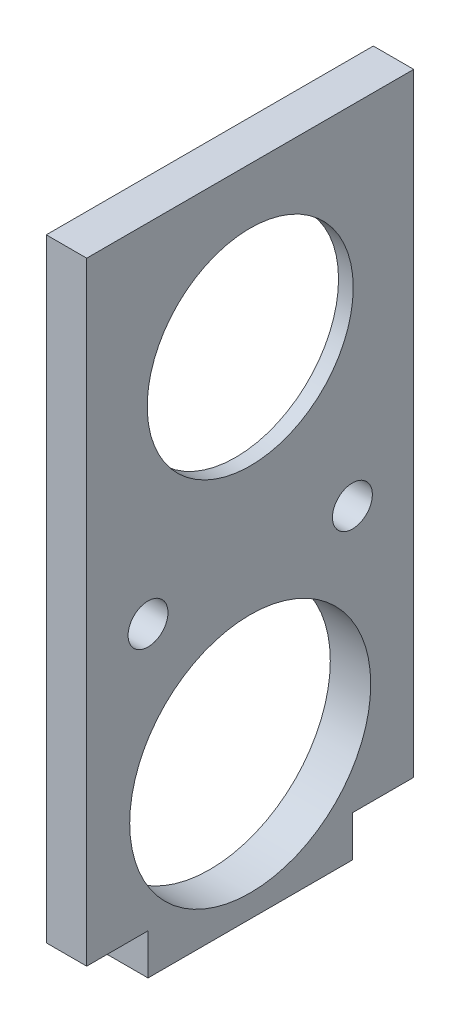
SolidWorks part; units mm, degrees
ref_plane "Front" through (0, 0, 0) normal (0, 0, 1) x (1, 0, 0)
ref_plane "Top" through (0, 0, 0) normal (0, 1, 0) x (1, 0, 0)
ref_plane "Right" through (0, 0, 0) normal (1, 0, 0) x (0, 0, -1)
sketch "Sketch1" plane through (0, 0, 0) normal (0, 0, 1) x (1, 0, 0)
  line L1 (-1.57, 25.4) -> (1.57, 25.4)
  line L2 (-1.57, 25.4) -> (-1.57, -25.4)
  line L3 (-1.57, -25.4) -> (1.57, -25.4)
  line L4 (1.57, 25.4) -> (1.57, -25.4)
extrude "Extrude1" add sketch "Sketch1" along normal blind 25.4
sketch "Sketch2" plane through (0, 0, 0) normal (1, 0, 0) x (0, 0, -1)
  line L1 (-25.4, -25.4) -> (-25.4, 25.4) construction
  line L2 (-25.4, -22.225) -> (-20.6375, -22.225)
  line L3 (-25.4, -22.225) -> (-25.4, -25.4)
  line L4 (-25.4, -25.4) -> (-20.6375, -25.4)
  line L6 (-20.6375, -22.225) -> (-20.6375, -25.4)
  line L7 (0, -25.4) -> (0, 25.4) construction
  line L8 (0, -22.225) -> (-4.7625, -22.225)
  line L9 (0, -22.225) -> (0, -25.4)
  line L10 (0, -25.4) -> (-4.7625, -25.4)
  line L11 (-4.7625, -22.225) -> (-4.7625, -25.4)
  line L12 (-25.4, -25.4) -> (0, -25.4) construction
  circle A0 centre (-12.7, -14.2875) radius 9.36
  circle A1 centre (-12.7, 13.0725) radius 8
  circle A2 centre (-20.6375, -1.5875) radius 1.55
  circle A3 centre (-4.7625, -1.5875) radius 1.55
extrude "Cut-Extrude1" cut sketch "Sketch2" against normal through all and the other way through all
sketch "Sketch3" plane through (-1.57, 0, 0) normal (-1, 0, 0) x (0, 0, 1)
  circle A0 centre (12.7, 13.0725) radius 11
extrude "Cut-Extrude2" cut sketch "Sketch3" against normal blind 2
